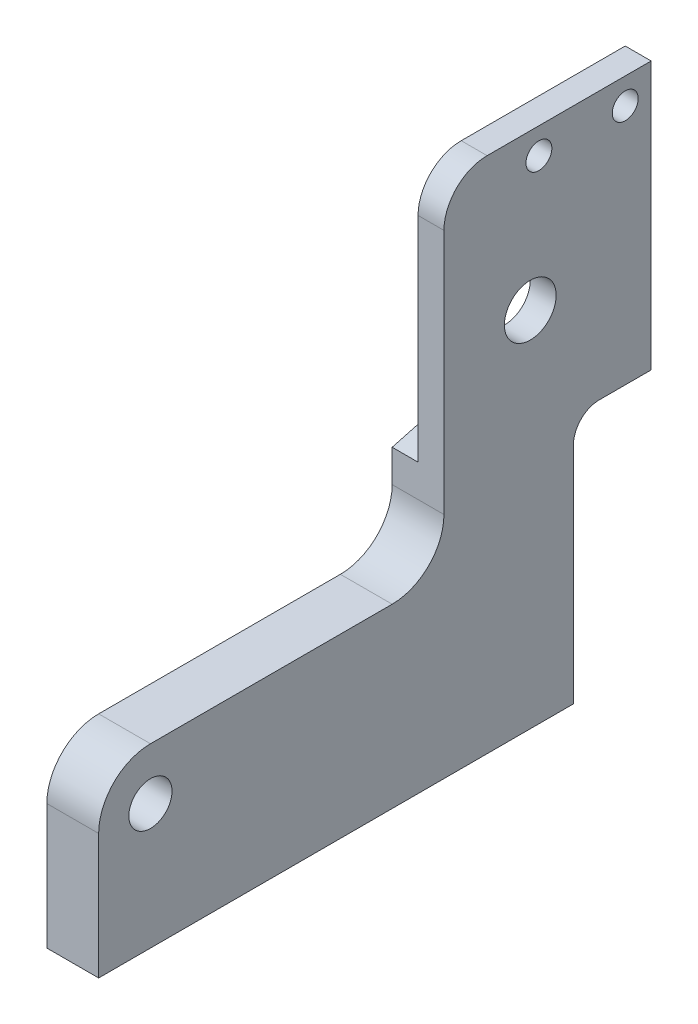
SolidWorks part; units mm, degrees
material "1060 Alloy"
ref_plane "Front Plane" through (0, 0, 0) normal (0, 0, 1) x (1, 0, 0)
ref_plane "Top Plane" through (0, 0, 0) normal (0, 1, 0) x (1, 0, 0)
ref_plane "Right Plane" through (0, 0, 0) normal (1, 0, 0) x (0, 0, -1)
sketch "Sketch1" plane through (0, 0, 0) normal (1, 0, 0) x (0, 0, -1)
  line L1 (0, 0) -> (64, 0)
  line L2 (0, 0) -> (0, 60)
  line L3 (0, 60) -> (64, 60)
  line L4 (64, 0) -> (64, 60)
  circle A0 centre (6, 14.5) radius 2.5
  circle A1 centre (50, 42) radius 3
  dimension "D1" = 6
  dimension "D2" = 5
  dimension "D3" = 14.5
  dimension "D4" = 6
  dimension "D5" = 42
  dimension "D6" = 50
  dimension "D7" = 64
  dimension "D8" = 60
extrude "Boss-Extrude1" add sketch "Sketch1" along normal blind 6
sketch "Sketch2" plane through (6, 0, 0) normal (1, 0, 0) x (0, 0, -1)
  line L0 (0, 60) -> (0, 0) construction
  line L2 (6, 20.5) -> (34, 20.5)
  line L4 (0, 14.5) -> (0, 61)
  line L5 (0, 61) -> (40, 61)
  line L6 (40, 61) -> (40, 26.5)
  line L7 (64, 60) -> (0, 60) construction
  arc A0 (0, 14.5) -> (6, 20.5) centre (6, 14.5) cw
  circle A1 centre (50, 42) radius 5 construction
  circle A2 centre (6, 14.5) radius 2.5 construction
  arc A4 (34, 20.5) -> (40, 26.5) centre (34, 26.5) ccw
  dimension "D2" = 10
  dimension "D1" = 1
  dimension "D3" = 40
extrude "Cut-Extrude1" cut sketch "Sketch2" against normal up to next
sketch "Sketch3" plane through (6, 0, 0) normal (1, 0, 0) x (0, 0, -1)
  line L0 (0, 14.5) -> (0, 0) construction
  line L57 (64, 0) -> (55, 0)
  line L58 (64, 0) -> (64, 29)
  line L59 (64, 29) -> (55, 29)
  line L60 (55, 0) -> (55, 29)
  dimension "D1" = 29
  dimension "D2" = 55
extrude "Cut-Extrude2" cut sketch "Sketch3" against normal up to next
fillet "Fillet1" radius 5 1 edges at (3, 60, -40)
fillet "Fillet2" radius 3 1 edges at (3, 29, -55)
hole_wizard "Tap Drill for M3 Tap1" positions "Sketch5" profile "Sketch4" hole size "M3" standard "ISO"
sketch "Sketch5" plane through (0, 0, 0) normal (0, -1, 0) x (-1, 0, 0)
  line L1 (-6, 0) -> (0, 0) construction
  line L2 (-6, 0) -> (-6, 55) construction
  point P0 (-3, 48)
  point P2 (-3, 12)
  dimension "D1" = 3
  dimension "D2" = 12
  dimension "D3" = 36
sketch "Sketch4" plane through (3, 0, -48) normal (1, 0, 0) x (0, 0, -1)
  line L0 (0, 0) -> (0, 10.7511)
  line L1 (0, 10.7511) -> (1.25, 10)
  line L2 (1.25, 10) -> (1.25, 0)
  line L5 (1.25, 0) -> (0, 0)
  line L10 (0, 10.7511) -> (-1.25, 10) construction
  line L11 (0, -6.35) -> (0, 107.95) construction
  dimension "Hole Dia." = 2.5
  dimension "Hole Depth" = 10
  dimension "Drill Angle" = 118
sketch "Sketch9" plane through (0, 0, 0) normal (-1, 0, 0) x (0, 0, 1)
  line L0 (-64, 60) -> (-64, 34)
  line L1 (-64, 60) -> (-45, 60) construction
  line L3 (-64, 29) -> (-64, 60) construction
  line L4 (-64, 60) -> (-40, 60)
  line L5 (-40, 60) -> (-40, 30.2487)
  line L6 (-54, 34) -> (-64, 34)
  line L11 (-40, 26.5) -> (-40, 55) construction
  line L12 (-40, 30.2487) -> (-54, 34)
  dimension "D1" = 10
  dimension "D2" = 26
  dimension "D5" = 75
extrude "Cut-Extrude3" cut sketch "Sketch9" against normal blind 3
sketch "Sketch10" plane through (3, 0, 0) normal (-1, 0, 0) x (0, 0, 1)
  line L0 (-45, 60) -> (-64, 60) construction
  line L1 (-64, 60) -> (-64, 34) construction
  circle A0 centre (-61, 57) radius 1.5
  circle A1 centre (-51, 57) radius 1.5
  dimension "D1" = 3
  dimension "D2" = 3
  dimension "D3" = 3
  dimension "D4" = 10
extrude "Cut-Extrude4" cut sketch "Sketch10" against normal up to next
